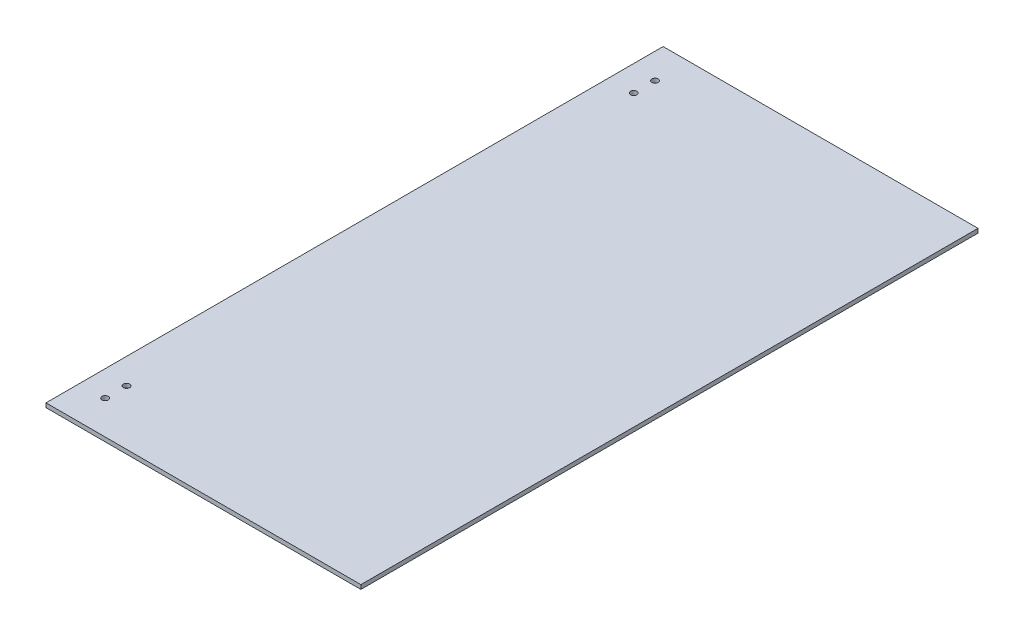
SolidWorks part; units mm, degrees
ref_plane "Front Plane" through (0, 0, 0) normal (0, 0, 1) x (1, 0, 0)
ref_plane "Top Plane" through (0, 0, 0) normal (0, 1, 0) x (1, 0, 0)
ref_plane "Right Plane" through (0, 0, 0) normal (1, 0, 0) x (0, 0, -1)
sketch "Sketch1" plane through (0, 0, 0) normal (0, 1, 0) x (1, 0, 0)
  line L1 (-75, 147) -> (75, 147)
  line L2 (-75, 147) -> (-75, -147)
  line L3 (-75, -147) -> (75, -147)
  line L4 (75, 147) -> (75, -147)
  line L5 (-75, 147) -> (75, -147) construction
  line L6 (-75, -147) -> (75, 147) construction
  point P0 (0, 0)
extrude "Boss-Extrude1" add sketch "Sketch1" along normal blind 2
sketch "Sketch2" plane through (0, 2, 0) normal (0, 1, 0) x (1, 0, 0)
  line L0 (-62.8273, -117.8577) -> (-62.8273, -88.4942) construction
  line L1 (75, 0) -> (142.505, 0) construction
  circle A0 centre (-62.8273, -130.9721) radius 1.5
  circle A1 centre (-62.8273, -120.7996) radius 1.5
  circle A2 centre (-62.8273, 120.7996) radius 1.5
  circle A3 centre (-62.8273, 130.9721) radius 1.5
extrude "Cut-Extrude1" cut sketch "Sketch2" against normal through all
